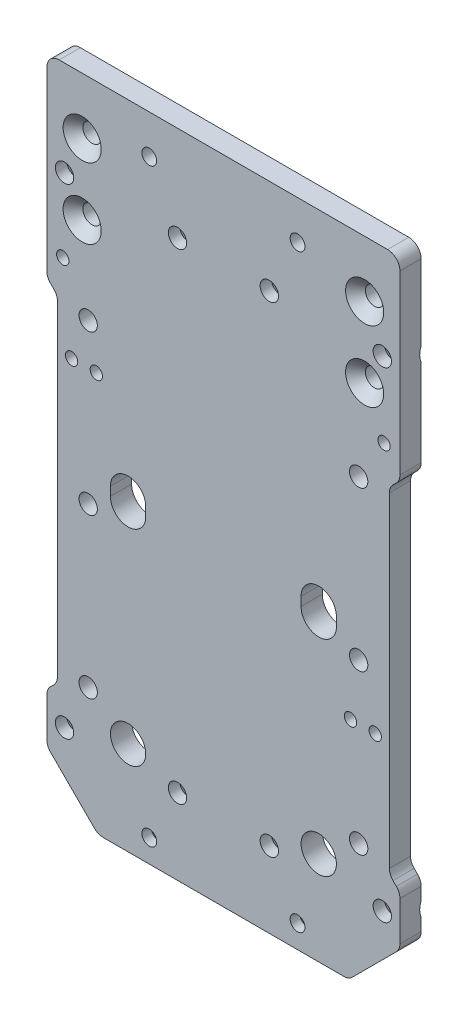
SolidWorks part; units mm, degrees
material "Acrylic (Medium-high impact)"
ref_plane "Front Plane" through (0, 0, 0) normal (0, 0, 1) x (1, 0, 0)
ref_plane "Top Plane" through (0, 0, 0) normal (0, 1, 0) x (1, 0, 0)
ref_plane "Right Plane" through (0, 0, 0) normal (1, 0, 0) x (0, 0, -1)
sketch "Sketch1" plane through (0, 0, 0) normal (0, 0, 1) x (1, 0, 0)
  line L0 (-50, 0) -> (-35.5, -14.5)
  line L1 (-50, 0) -> (50, 0)
  line L2 (-50, 0) -> (-50, 170)
  line L3 (-50, 170) -> (50, 170)
  line L4 (50, 0) -> (50, 170)
  line L5 (-35.5, -14.5) -> (35.5, -14.5)
  line L6 (35.5, -14.5) -> (50, 0)
  line L7 (0, 0) -> (0, 178.5984) construction
  point P4 (0, 0)
  point P8 (0, -14.5)
  dimension "D1" = 100
  dimension "D2" = 170
  dimension "D3" = 14.5
  dimension "D4" = 45
extrude "Body" add sketch "Sketch1" along normal mid plane 6 contours L1 L4 L3 L2 | L5 L6 L1 L0 | L1 L7 L3 L2 region at (0, -6.8402, 0) region at (-25, 85, 0) region at (25, 85, 0)
sketch "Sketch2" plane through (0, 0, 3) normal (0, 0, 1) x (1, 0, 0)
  line L0 (0, 0) -> (0, 32.3546) construction
  circle A0 centre (-38.3, 20.2) radius 2.6
  circle A1 centre (38.3, 20.2) radius 2.6
  circle A2 centre (-38.3, 110.2) radius 2.6
  circle A3 centre (38.3, 110.2) radius 2.6
  circle A4 centre (-38.3, 65.2) radius 2.6
  circle A5 centre (38.3, 65.2) radius 2.6
  dimension "D1" = 76.6
  dimension "D2" = 5.2
  dimension "D3" = 20.2
  dimension "D4" = 90
  dimension "D5" = 45
extrude "MountToBaseHoles" cut sketch "Sketch2" against normal through all
sketch "Sketch3" plane through (0, 0, 3) normal (0, 0, 1) x (1, 0, 0)
  line L0 (-13, 7) -> (-45, 7) construction
  line L1 (-38.3, 110.2) -> (-77.9825, 110.2) construction
  line L2 (13, 7) -> (13, 37.5378) construction
  line L4 (-13, 7) -> (-13, 44.3761) construction
  line L5 (0, 0) -> (0, 40.72) construction
  circle A0 centre (-45, 7) radius 2.6
  circle A1 centre (-45, 143.1) radius 2.6
  circle A2 centre (45, 143.1) radius 2.6
  circle A3 centre (45, 7) radius 2.6
  circle A6 centre (-13, 143.1) radius 2.6
  circle A7 centre (13, 143.1) radius 2.6
  circle A8 centre (-13, 7) radius 2.6
  circle A9 centre (13, 7) radius 2.6
  dimension "D1" = 5.2
  dimension "D4" = 136.1
  dimension "D6" = 32
  dimension "D2" = 32
  dimension "D3" = 26
  dimension "D7" = 13
  dimension "D5" = 7
extrude "MountRodHoles" cut sketch "Sketch3" against normal through all
sketch "Sketch4" plane through (0, 0, -3) normal (0, 0, -1) x (-1, 0, 0)
  line L1 (0, 0) -> (0, 34.6557) construction
  line L2 (50, 170) -> (-50, 170) construction
  circle A0 centre (-40, 154) radius 2.6
  circle A2 centre (40, 154) radius 2.6
  circle A4 centre (40, 134) radius 2.6
  circle A6 centre (-40, 134) radius 2.6
  dimension "D4" = 5.2
  dimension "D1" = 16
  dimension "D2" = 40
  dimension "D5" = 20
extrude "MountAngleCornerHoles" cut sketch "Sketch4" against normal through all
chamfer "ChamferForSlottedFlatHeadScrews" distance 2.8 angle 45 12 edges at (-10.4, 7, -3) (15.6, 7, -3) (-42.4, 143.1, -3) (-10.4, 143.1, -3) (15.6, 143.1, -3) (47.6, 143.1, -3) (-42.4, 7, -3) (47.6, 7, -3) (-42.6, 154, 3) (-42.6, 134, 3) (37.4, 154, 3) (37.4, 134, 3)
sketch "Sketch6" plane through (0, 0, 3) normal (0, 0, 1) x (1, 0, 0)
  line L0 (-50, 115) -> (-47, 112)
  line L1 (0, 0) -> (0, 25.1631) construction
  line L2 (-47, 112) -> (-47, 17)
  line L3 (-47, 17) -> (-50, 14)
  line L4 (50, 115) -> (47, 112)
  line L6 (47, 112) -> (47, 17)
  line L7 (47, 17) -> (50, 14)
  line L8 (-50, 115) -> (-50, 14)
  line L9 (50, 115) -> (50, 14)
  line L12 (-50, 0) -> (-50, 170) construction
  line L13 (50, 0) -> (50, 170) construction
  dimension "D1" = 3
  dimension "D2" = 3
  dimension "D3" = 45
  dimension "D5" = 115
  dimension "D4" = 14
extrude "ReduceSomeWidth" cut sketch "Sketch6" against normal through all
sketch "screwHeadHoleCarriageY" plane through (0, 0, -3) normal (0, 0, -1) x (-1, 0, 0)
  line L0 (0, 0) -> (0, 34.2129) construction
  line L1 (35.5, -14.5) -> (-35.5, -14.5) construction
  line L2 (-27, 70.2) -> (-27, 72.7) construction
  line L3 (-32, 70.2) -> (-32, 72.7)
  line L4 (-22, 70.2) -> (-22, 72.7)
  line L5 (27, 70.2) -> (27, 72.7) construction
  line L6 (22, 70.2) -> (22, 72.7)
  line L7 (32, 70.2) -> (32, 72.7)
  circle A0 centre (-27, 12) radius 5
  circle A1 centre (27, 12) radius 5
  arc A6 (-32, 70.2) -> (-22, 70.2) centre (-27, 70.2) ccw
  arc A7 (-22, 72.7) -> (-32, 72.7) centre (-27, 72.7) ccw
  arc A8 (22, 70.2) -> (32, 70.2) centre (27, 70.2) ccw
  arc A9 (32, 72.7) -> (22, 72.7) centre (27, 72.7) ccw
  point P18 (-27, 71.45)
  point P28 (27, 71.45)
  dimension "D3" = 10
  dimension "D5" = 12.5
  dimension "D1" = 54
  dimension "D2" = 26.5
  dimension "D4" = 84.7
extrude "CutForOtherScrewsHeads" cut sketch "screwHeadHoleCarriageY" against normal through all
sketch "Sketch7" plane through (0, 0, 3) normal (0, 0, 1) x (1, 0, 0)
  line L0 (-35.5, -14.5) -> (35.5, -14.5) construction
  line L2 (50, 0) -> (50, 14) construction
  line L3 (-50, 0) -> (-50, 14) construction
  circle A0 centre (43, 49.5) radius 1.75
  circle A1 centre (36, 49.5) radius 1.75
  circle A2 centre (-36, 98.5) radius 1.75
  circle A3 centre (-43, 98.5) radius 1.75
  dimension "D3" = 3.5
  dimension "D1" = 64
  dimension "D2" = 7
  dimension "D4" = 7
  dimension "D5" = 7
  dimension "D6" = 7
  dimension "D7" = 113
extrude "EndSensorsHoles" cut sketch "Sketch7" against normal through all
chamfer "ChamferEndSensors" distance 1.5 angle 45 4 edges at (37.75, 49.5, -3) (44.75, 49.5, -3) (-41.25, 98.5, -3) (-34.25, 98.5, -3)
fillet "EndMillMinimumRadius" radius 3.5 14 edges at (-50, 170, 0) (50, 170, 0) (47, 112, 0) (47, 17, 0) (-47, 17, 0) (-47, 112, 0) (-50, 14, 0) (-50, 0, 0) (-35.5, -14.5, 0) (50, 14, 0) (50, 0, 0) (35.5, -14.5, 0) (-50, 115, 0) (50, 115, 0)
hole_wizard "Ø3.5 (3.5) CableTieHoles" positions "Sketch9" profile "Sketch10" hole size "Ø3.5" standard "ANSI Metric" end condition through all
sketch "Sketch9" plane through (0, 0, -3) normal (0, 0, -1) x (-1, 0, 0)
  line L0 (-50, 116.4497) -> (-50, 141.0604) construction
  line L1 (50, 116.4497) -> (50, 141.0604) construction
  line L2 (34.0503, -14.5) -> (-34.0503, -14.5) construction
  point P0 (-45.5, 122)
  point P2 (45.5, 122)
  point P7 (0, 0)
  dimension "D1" = 4.5
  dimension "D2" = 4.5
  dimension "D3" = 136.5
sketch "Sketch10" plane through (45.5, 122, -3) normal (1, 0, 0) x (0, 1, 0)
  line L0 (0, 0) -> (0, 6)
  line L1 (0, 6) -> (1.75, 6)
  line L2 (1.75, 6) -> (1.75, 0)
  line L5 (1.75, 0) -> (0, 0)
  line L11 (0, -6.35) -> (0, 107.95) construction
  dimension "Thru Hole Dia." = 3.5
  dimension "Thru Hole Depth" = 6
hole_wizard "Ø4.2 (4.2) KP8 Holes1" positions "Sketch11" profile "Sketch12" hole size "Ø4.2" standard "ANSI Metric" end condition through all
sketch "Sketch11" plane through (0, 0, -3) normal (0, 0, -1) x (-1, 0, 0)
  line L0 (34.0503, -14.5) -> (-34.0503, -14.5) construction
  line L2 (0, 0) -> (0, 41.1682) construction
  point P0 (-21, 159)
  point P2 (21, 159)
  dimension "D1" = 42
  dimension "D2" = 173.5
sketch "Sketch12" plane through (21, 159, -3) normal (1, 0, 0) x (0, 1, 0)
  line L0 (0, 0) -> (0, 6)
  line L1 (0, 6) -> (2.1, 6)
  line L2 (2.1, 6) -> (2.1, 0)
  line L5 (2.1, 0) -> (0, 0)
  line L11 (0, -6.35) -> (0, 107.95) construction
  dimension "Thru Hole Dia." = 4.2
  dimension "Thru Hole Depth" = 6
hole_wizard "Ø4.2 (4.2) KP8 Holes2" positions "Sketch13" profile "Sketch14" hole size "Ø4.2" standard "ANSI Metric" end condition through all
sketch "Sketch13" plane through (0, 0, -3) normal (0, 0, -1) x (-1, 0, 0)
  line L0 (34.0503, -14.5) -> (-34.0503, -14.5) construction
  line L1 (0, 0) -> (0, 17.4832) construction
  point P0 (-21, -8)
  point P2 (21, -8)
  point P14 (0, 0)
  dimension "D1" = 42
  dimension "D2" = 6.5
sketch "Sketch14" plane through (21, -8, -3) normal (1, 0, 0) x (0, 1, 0)
  line L0 (0, 0) -> (0, 6)
  line L1 (0, 6) -> (2.1, 6)
  line L2 (2.1, 6) -> (2.1, 3.3)
  line L3 (2.1, 3.3) -> (5.4, 0)
  line L5 (5.4, 0) -> (0, 0)
  line L6 (-2.1, 3.3) -> (-5.4, 0) construction
  line L11 (0, -6.35) -> (0, 107.95) construction
  dimension "Thru Hole Dia." = 4.2
  dimension "Thru Hole Depth" = 6
  dimension "Near C'Sink Dia." = 10.8
  dimension "Near C'Sink Angle" = 90
equation "\"D6@Sketch3\"=\"D2@Sketch3\""
equation "\"D7@Sketch3\"=\"D3@Sketch3\"/2"
equation "\"D1@Sketch6\"=\"D2@Sketch6\""
